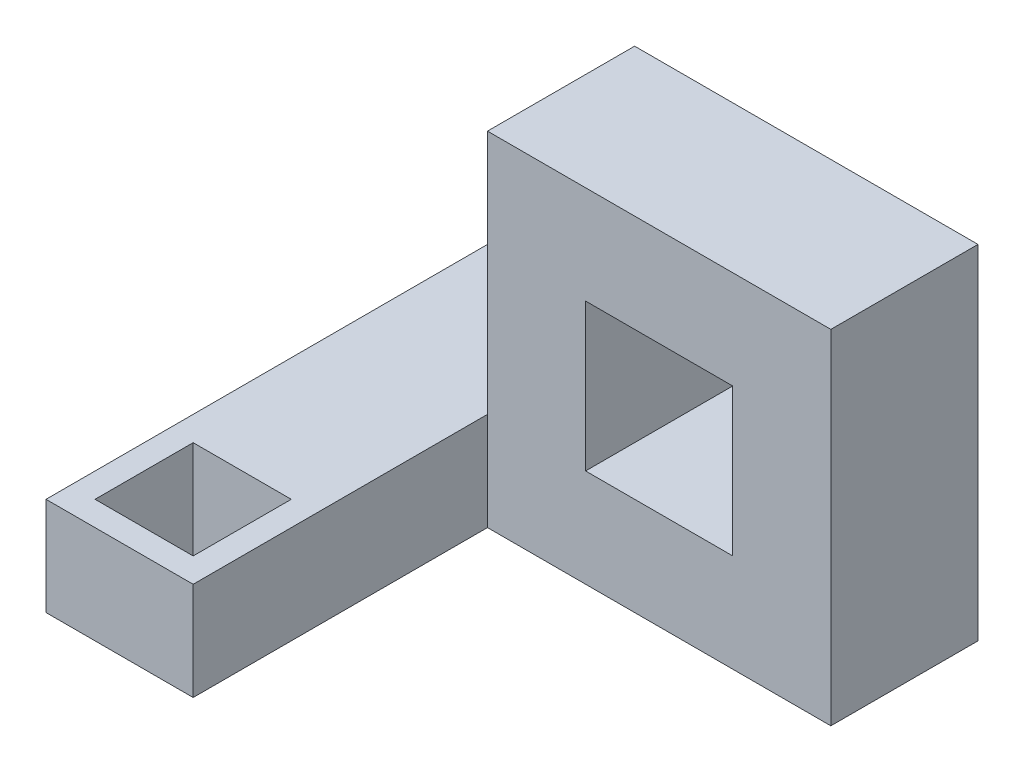
SolidWorks part; units mm, degrees
ref_plane "Front Plane" through (0, 0, 0) normal (0, 0, 1) x (1, 0, 0)
ref_plane "Top Plane" through (0, 0, 0) normal (0, 1, 0) x (1, 0, 0)
ref_plane "Right Plane" through (0, 0, 0) normal (1, 0, 0) x (0, 0, -1)
sketch "Sketch1" plane through (0, 0, 0) normal (0, 0, 1) x (1, 0, 0)
  line L1 (-17.5, -17.5) -> (17.5, -17.5)
  line L2 (-17.5, -17.5) -> (-17.5, 17.5)
  line L3 (-17.5, 17.5) -> (17.5, 17.5)
  line L4 (17.5, -17.5) -> (17.5, 17.5)
  line L5 (-17.5, -17.5) -> (17.5, 17.5) construction
  line L6 (-17.5, 17.5) -> (17.5, -17.5) construction
  point P0 (0, 0)
  dimension "D1" = 35
  dimension "D2" = 35
extrude "Boss-Extrude1" add sketch "Sketch1" along normal blind 15
sketch "Sketch2" plane through (0, 0, 15) normal (0, 0, 1) x (1, 0, 0)
  line L1 (-7.5, -7.5) -> (7.5, -7.5)
  line L2 (-7.5, -7.5) -> (-7.5, 7.5)
  line L3 (-7.5, 7.5) -> (7.5, 7.5)
  line L4 (7.5, -7.5) -> (7.5, 7.5)
  line L5 (-7.5, -7.5) -> (7.5, 7.5) construction
  line L6 (-7.5, 7.5) -> (7.5, -7.5) construction
  point P0 (0, 0)
  dimension "D1" = 15
  dimension "D3" = 15
extrude "Cut-Extrude1" cut sketch "Sketch2" against normal blind 54
sketch "Sketch4" plane through (0, 0, 0) normal (0, 0, -1) x (-1, 0, 0)
  line L0 (17.5, -17.5) -> (17.5, -7.5021)
  line L1 (17.5, -17.5) -> (32.5, -17.5)
  line L2 (17.5, -7.5021) -> (32.5, -7.5021)
  line L3 (32.5, -17.5) -> (32.5, -7.5021)
  line L4 (17.5, 17.5) -> (17.5, -17.5) construction
  dimension "D1" = 15
  dimension "D2" = 9.9979
extrude "Boss-Extrude2" add sketch "Sketch4" against normal blind 45
sketch "Sketch5" plane through (0, -17.5, 0) normal (0, -1, 0) x (1, 0, 0)
  line L0 (-32.5, 45) -> (-32.5, 0) construction
  line L1 (-30, 32.5) -> (-20, 32.5)
  line L2 (-30, 32.5) -> (-30, 42.5)
  line L3 (-30, 42.5) -> (-20, 42.5)
  line L4 (-20, 32.5) -> (-20, 42.5)
  line L5 (-30, 32.5) -> (-20, 42.5) construction
  line L6 (-30, 42.5) -> (-20, 32.5) construction
  line L8 (-17.5, 45) -> (-32.5, 45) construction
  point P0 (-25, 37.5)
  dimension "D1" = 10
  dimension "D2" = 10
  dimension "D3" = 2.5
  dimension "D4" = 2.5
extrude "Cut-Extrude2" cut sketch "Sketch5" against normal blind 45
